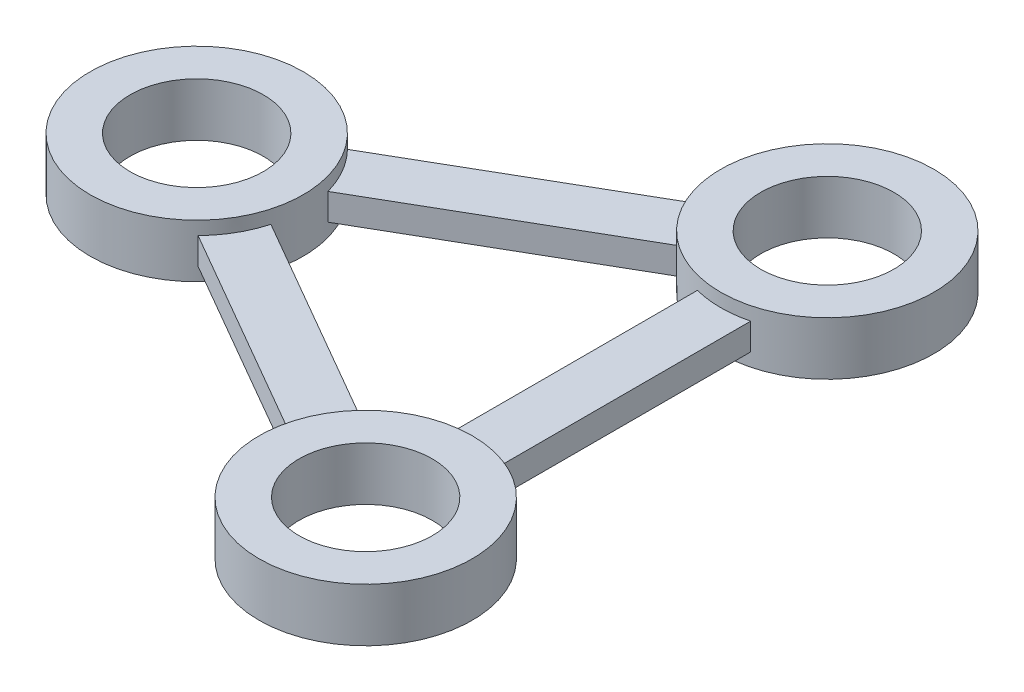
SolidWorks part; units mm, degrees
ref_plane "Front Plane" through (0, 0, 0) normal (0, 0, 1) x (1, 0, 0)
ref_plane "Top Plane" through (0, 0, 0) normal (0, 1, 0) x (1, 0, 0)
ref_plane "Right Plane" through (0, 0, 0) normal (1, 0, 0) x (0, 0, -1)
sketch "Sketch1" plane through (0, 0, 0) normal (0, 1, 0) x (1, 0, 0)
  line L0 (-150, 0) -> (131.6509, 0) construction
  line L1 (0, 86.6) -> (0, -86.6) construction
  circle A0 centre (-150, 0) radius 40
  circle A1 centre (-150, 0) radius 25
  circle A2 centre (0, 86.6) radius 40
  circle A3 centre (0, 86.6) radius 25
  circle A4 centre (0, -86.6) radius 25
  circle A5 centre (0, -86.6) radius 40
  point P12 (0, 0)
  dimension "D1" = 80
  dimension "D2" = 80
  dimension "D3" = 50
  dimension "D4" = 150
  dimension "D5" = 173.2
extrude "Boss-Extrude1" add sketch "Sketch1" along normal blind 10 and the other way blind 10
sketch "Sketch2" plane through (0, 0, 0) normal (0, 1, 0) x (1, 0, 0)
  line L0 (0, 86.6) -> (0, -86.6) construction
  line L1 (-150, 0) -> (0, 86.6) construction
  line L2 (-150, 0) -> (0, -86.6) construction
  line L3 (10, 47.8702) -> (10, -47.8702)
  line L4 (-10, 47.8702) -> (-10, -47.8702)
  line L5 (-111.4588, 10.7042) -> (-28.5414, 58.5752)
  line L6 (-121.4586, 28.0248) -> (-38.5412, 75.8958)
  line L7 (-111.4588, -10.7042) -> (-28.5414, -58.5752)
  line L8 (-121.4586, -28.0248) -> (-38.5412, -75.8958)
  circle A0 centre (0, 86.6) radius 40 construction
  circle A1 centre (0, -86.6) radius 40 construction
  arc A2 (-10, 47.8702) -> (10, 47.8702) centre (0, 86.6) ccw
  arc A3 (-28.5414, -58.5752) -> (-38.5412, -75.8958) centre (0, -86.6) ccw
  arc A4 (-111.4588, 10.7042) -> (-121.4586, 28.0248) centre (-150, 0) ccw
  arc A5 (10, -47.8702) -> (-10, -47.8702) centre (0, -86.6) ccw
  arc A6 (-121.4586, -28.0248) -> (-111.4588, -10.7042) centre (-150, 0) ccw
  arc A7 (-38.5412, 75.8958) -> (-28.5414, 58.5752) centre (0, 86.6) ccw
  dimension "D1" = 80
  dimension "D2" = 80
  dimension "D4" = 20
  dimension "D5" = 20
  dimension "D6" = 20
extrude "Boss-Extrude2" add sketch "Sketch2" along normal blind 5 and the other way blind 5
